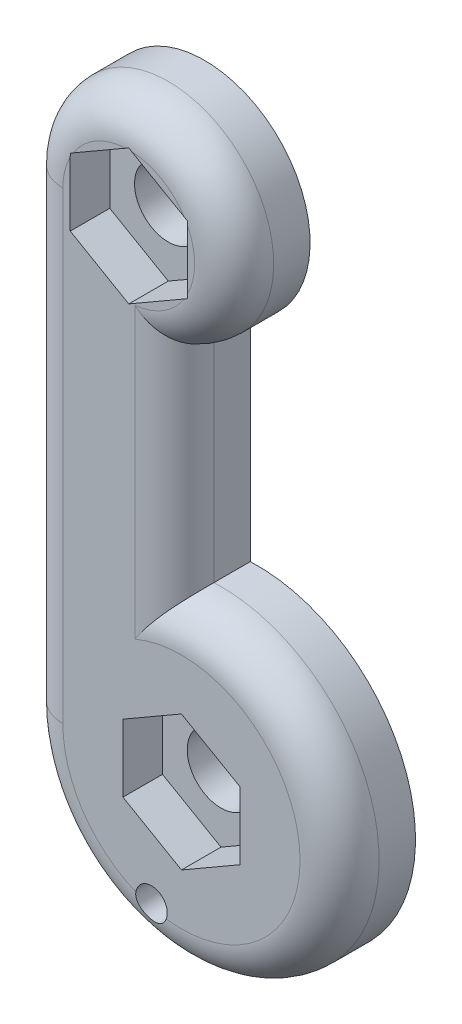
SolidWorks part; units mm, degrees
ref_plane "Front Plane" through (0, 0, 0) normal (0, 0, 1) x (1, 0, 0)
ref_plane "Top Plane" through (0, 0, 0) normal (0, 1, 0) x (1, 0, 0)
ref_plane "Right Plane" through (0, 0, 0) normal (1, 0, 0) x (0, 0, -1)
sketch "Sketch1" plane through (0, 0, 0) normal (0, 0, 1) x (1, 0, 0)
  line L0 (-7.5, 22) -> (-7.5, 0)
  line L2 (-0.3362, 7.4925) -> (-0.3362, 17.4925)
  circle A0 centre (0, 0) radius 1.6
  arc A1 (-7.5, 0) -> (-0.3362, 7.4925) centre (0, 0) ccw
  circle A2 centre (-2.5, 22) radius 1.6
  arc A3 (-0.3362, 17.4925) -> (-7.5, 22) centre (-2.5, 22) ccw
  dimension "D2" = 10
  dimension "D3" = 3.2
  dimension "D4" = 15
  dimension "D5" = 10
  dimension "D6" = 22
extrude "Boss-Extrude1" add sketch "Sketch1" along normal blind 3.6
sketch "Sketch2" plane through (0, 0, 3.6) normal (0, 0, 1) x (1, 0, 0)
  line L0 (0, 0) -> (-1.4235, -5.3126) construction
  line L2 (0, 0) -> (0, 1.6) construction
  circle A0 centre (-1.4235, -5.3126) radius 0.75
  circle A1 centre (0, 0) radius 1.6 construction
  dimension "D2" = 1.5
  dimension "D1" = 5.5
  dimension "D3" = 165
extrude "Cut-Extrude1" cut sketch "Sketch2" against normal through all
sketch "Sketch3" plane through (0, 0, 3.6) normal (0, 0, 1) x (1, 0, 0)
  line L1 (0, 3.2043) -> (-2.775, 1.6021)
  line L2 (-2.775, 1.6021) -> (-2.775, -1.6021)
  line L3 (-2.775, -1.6021) -> (0, -3.2043)
  line L4 (0, -3.2043) -> (2.775, -1.6021)
  line L5 (2.775, -1.6021) -> (2.775, 1.6021)
  line L6 (2.775, 1.6021) -> (0, 3.2043)
  line L7 (-2.5, 18.7957) -> (0.275, 20.3979)
  line L8 (0.275, 20.3979) -> (0.275, 23.6021)
  line L9 (0.275, 23.6021) -> (-2.5, 25.2043)
  line L10 (-2.5, 25.2043) -> (-5.275, 23.6021)
  line L11 (-5.275, 23.6021) -> (-5.275, 20.3979)
  line L12 (-5.275, 20.3979) -> (-2.5, 18.7957)
  circle A0 centre (0, 0) radius 2.775 construction
  circle A1 centre (-2.5, 22) radius 2.775 construction
  dimension "D1" = 5.55
extrude "Cut-Extrude2" cut sketch "Sketch3" against normal blind 1.875
sketch "Sketch4" [suppressed] plane through (0, 0, 0) normal (0, 0, -1) x (-1, 0, 0)
  line L1 (0, 3.1754) -> (-2.75, 1.5877)
  line L2 (-2.75, 1.5877) -> (-2.75, -1.5877)
  line L3 (-2.75, -1.5877) -> (0, -3.1754)
  line L4 (0, -3.1754) -> (2.75, -1.5877)
  line L5 (2.75, -1.5877) -> (2.75, 1.5877)
  line L6 (2.75, 1.5877) -> (0, 3.1754)
  circle A1 centre (2.5, 22) radius 2.775
  circle A2 centre (0, 0) radius 2.75 construction
  dimension "D1" = 5.55
  dimension "D2" = 5.5
extrude "Cut-Extrude3" [suppressed] cut sketch "Sketch4" against normal blind 1.875
fillet "Fillet1" radius 1.875 4 edges at (0.1628, 26.232, 3.6) (5.4209, -5.1831, 3.6) (-0.3362, 12.4925, 3.6) (-7.5, 11, 3.6)
fillet "Fillet2" [suppressed] radius 1.875
